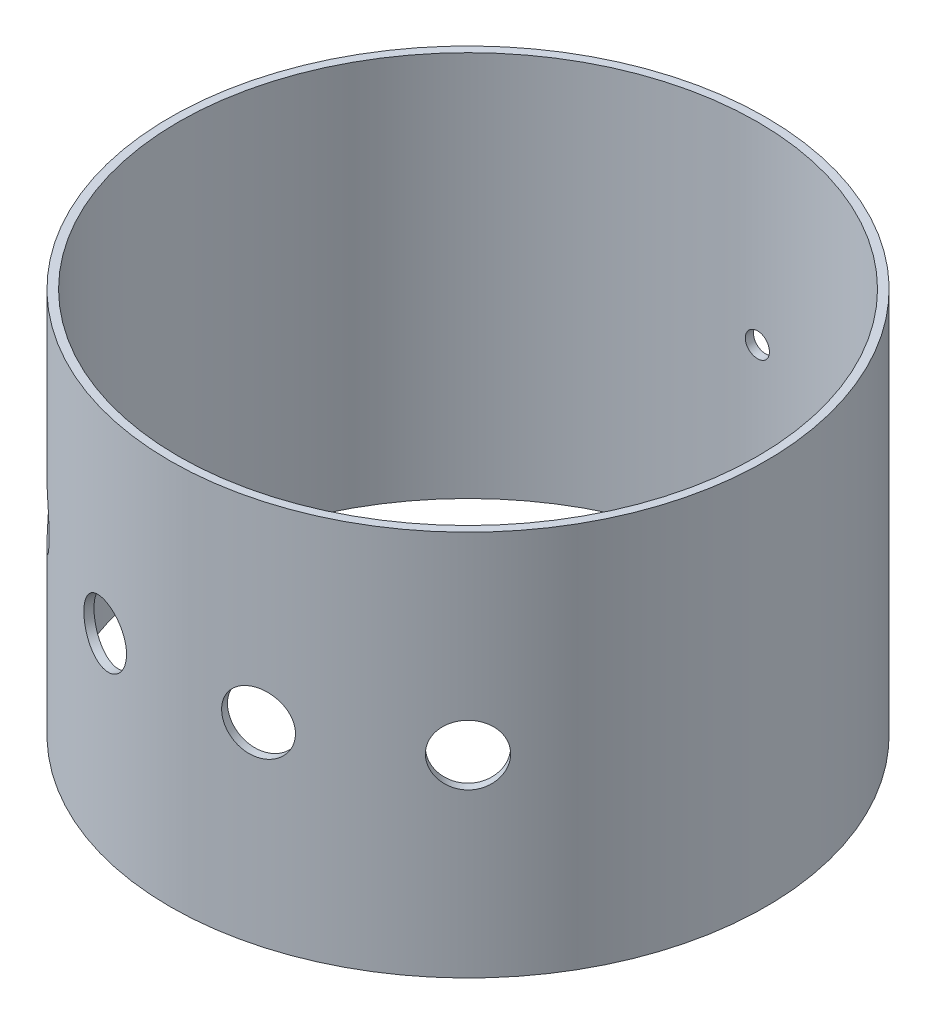
SolidWorks part; units mm, degrees
material "C-Glass Fiber"
ref_plane "Front Plane" through (0, 0, 0) normal (0, 0, 1) x (1, 0, 0)
ref_plane "Top Plane" through (0, 0, 0) normal (0, 1, 0) x (1, 0, 0)
ref_plane "Right Plane" through (0, 0, 0) normal (1, 0, 0) x (0, 0, -1)
sketch "Body Tube Profile" plane through (0, 0, 0) normal (0, 1, 0) x (1, 0, 0)
  circle A0 centre (0, 0) radius 76.2
  circle A1 centre (0, 0) radius 78.359
  dimension "D1" = 152.4
  dimension "D2" = 156.718
extrude "Body Tube Extrustion" add sketch "Body Tube Profile" along normal blind 101.6
sketch "Center Axis" plane through (0, 0, 0) normal (0, 0, 1) x (1, 0, 0)
  line L0 (0, 0) -> (0, 101.6) construction
  line L1 (76.2, 101.6) -> (-76.2, 101.6) construction
ref_plane "Offset Cut Plane" through (0, 0, 0) normal (0.7071, 0, 0.7071) x (0, 1, 0)
sketch "Sketch2" plane through (0, 0, 0) normal (0.7071, 0, 0.7071) x (0, 1, 0)
  line L0 (50.8, 78.359) -> (50.8, -78.359) construction
  line L1 (101.6, 78.359) -> (0, 78.359) construction
  line L2 (0, -78.359) -> (101.6, -78.359) construction
  circle A0 centre (50.8, 0) radius 7.9375
  dimension "D1" = 15.875
extrude "Key Hole Cut" cut sketch "Sketch2" along normal through all
pattern_circular "Key Hole Pattern" count 4 over 90 about axis through (0, 101.6, 0) along (0, 1, 0) of "Key Hole Cut" reverse direction yes
sketch "Sketch3" plane through (0, 0, 0) normal (0, 0, 1) x (1, 0, 0)
  line L0 (-78.359, 50.8) -> (78.359, 50.8) construction
  line L1 (-78.359, 101.6) -> (-78.359, 0) construction
  line L2 (78.359, 0) -> (78.359, 101.6) construction
  circle A0 centre (0, 50.8) radius 3.175
  dimension "D1" = 6.35
extrude "Cut-Extrude1" cut sketch "Sketch3" against normal through all
equation "\"Length\"=4"
equation "\"Outer Diameter\"= 6.17"
equation "\"Inner Diameter\"= 6"
equation "\"Wall Thickness\"= 0.085"
equation "\"D1@Body Tube Profile\" = \"Inner Diameter\""
equation "\"D2@Body Tube Profile\" = \"Outer Diameter\""
equation "\"D1@Body Tube Extrustion\" = \"Length\""
equation "\"Key Hole Dia\"= 0.625"
equation "\"Hole Angle 1\"= 15"
equation "\"Hole Angle 2\"= 45"
equation "\"D1@Sketch2\"=\"Key Hole Dia\""
